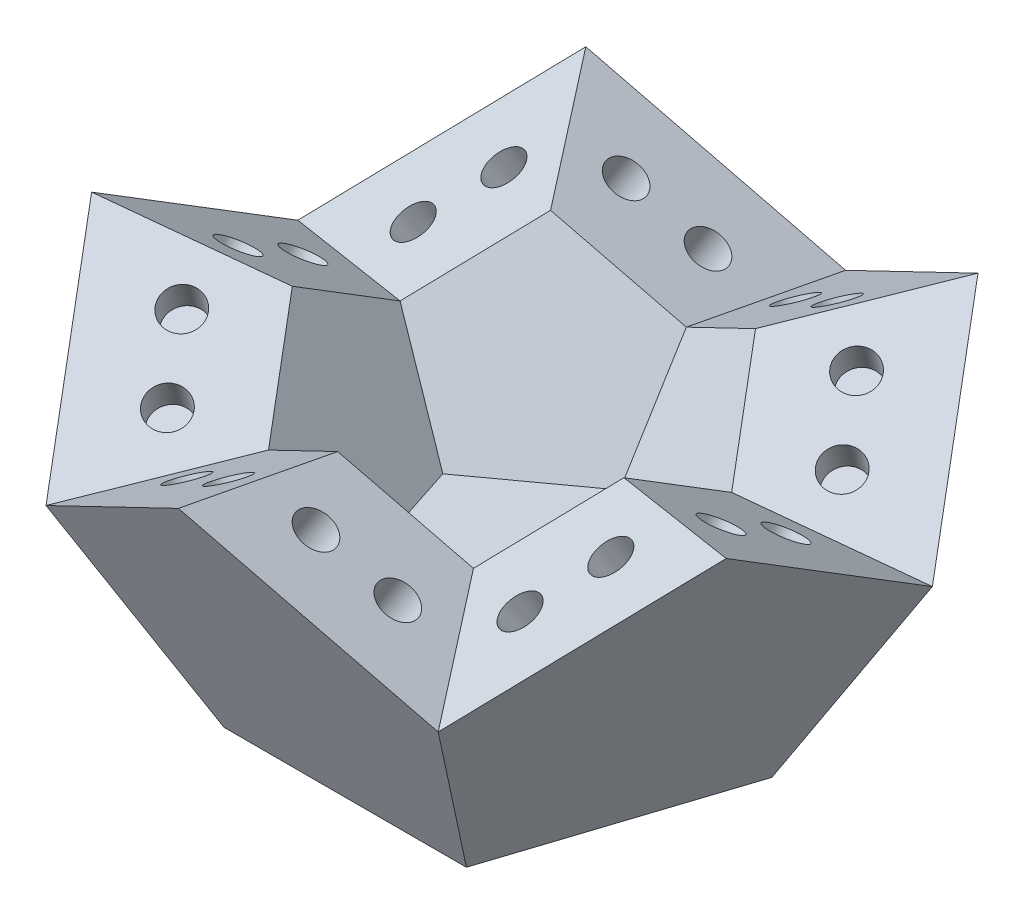
SolidWorks part; units mm, degrees
ref_plane "Front Plane" through (0, 0, 0) normal (0, 0, 1) x (1, 0, 0)
ref_plane "Top Plane" through (0, 0, 0) normal (0, 1, 0) x (1, 0, 0)
ref_plane "Right Plane" through (0, 0, 0) normal (1, 0, 0) x (0, 0, -1)
ref_axis "Axis1" through (0, 14.8487, 0) along (0, -1, 0)
sketch "Sketch1" plane through (0, 0, 0) normal (0, 1, 0) x (1, 0, 0)
  line L1 (0, 10.8033) -> (-10.2745, 3.3384)
  line L2 (-10.2745, 3.3384) -> (-6.35, -8.74)
  line L3 (-6.35, -8.74) -> (6.35, -8.74)
  line L4 (6.35, -8.74) -> (10.2745, 3.3384)
  line L5 (10.2745, 3.3384) -> (0, 10.8033)
  circle A0 centre (0, 0) radius 8.74 construction
  dimension "D1" = 12.7
extrude "Boss-Extrude1" add sketch "Sketch1" along normal blind 6.752 draft 31.717
sketch "Sketch3" plane through (0, 3.9087, 6.3243) normal (0, 0.5257, 0.8507) x (1, 0, 0)
  line L0 (-2, -0.6262) -> (2, -0.6262) construction
  line L1 (-6.35, -4.5949) -> (6.35, -4.5949) construction
  line L2 (-2, -4.5949) -> (-2, 3.3426) construction
  circle A0 centre (-2, -0.6262) radius 1
  circle A1 centre (2, -0.6262) radius 1
  point P4 (0, -0.6262)
  point P5 (-2, -0.6262)
  dimension "D1" = 2
  dimension "D2" = 4
  dimension "D3" = 7.9375
extrude "Cut-Extrude1" cut sketch "Sketch3" against normal blind 2
pattern_circular "CirPattern1" count 5 over 360 about axis through (0, 14.8487, 0) along (0, -1, 0) of "Cut-Extrude1"
mirror "Mirror1" about plane through (0, 0, -10.8033) normal (-0.5, 0.5257, -0.6882) of "CirPattern1", "Cut-Extrude1", "Boss-Extrude1"
mirror "Mirror2" about plane through (-10.2745, 0, -3.3384) normal (-0.809, 0.5257, 0.2629) of "CirPattern1", "Cut-Extrude1", "Boss-Extrude1"
mirror "Mirror3" about plane through (-6.35, 0, 8.74) normal (0, 0.5257, 0.8507) of "Boss-Extrude1", "CirPattern1", "Cut-Extrude1"
mirror "Mirror4" about plane through (6.35, 0, 8.74) normal (0.809, 0.5257, 0.2629) of "CirPattern1", "Cut-Extrude1", "Boss-Extrude1"
mirror "Mirror5" about plane through (10.2745, 0, -3.3384) normal (0.5, 0.5257, -0.6882) of "Boss-Extrude1", "CirPattern1", "Cut-Extrude1"
equation "\"angle\"= arccos ( - sqr ( 5 ) / 5 )"
equation "\"theta\"= 90 - \"angle\" / 2"
equation "\"side\"=0.5"
equation "\"D1@Sketch1\"=\"side\""
equation "\"D3@Boss-Extrude1\"=\"theta\""
equation "\"D1@Boss-Extrude1\"=\"height\""
equation "\"face_height\"= .3125in"
equation "\"height\"= \"face_height\" * cos ( \"theta\" )"
equation "\"D3@Sketch3\"=\"face_height\""
